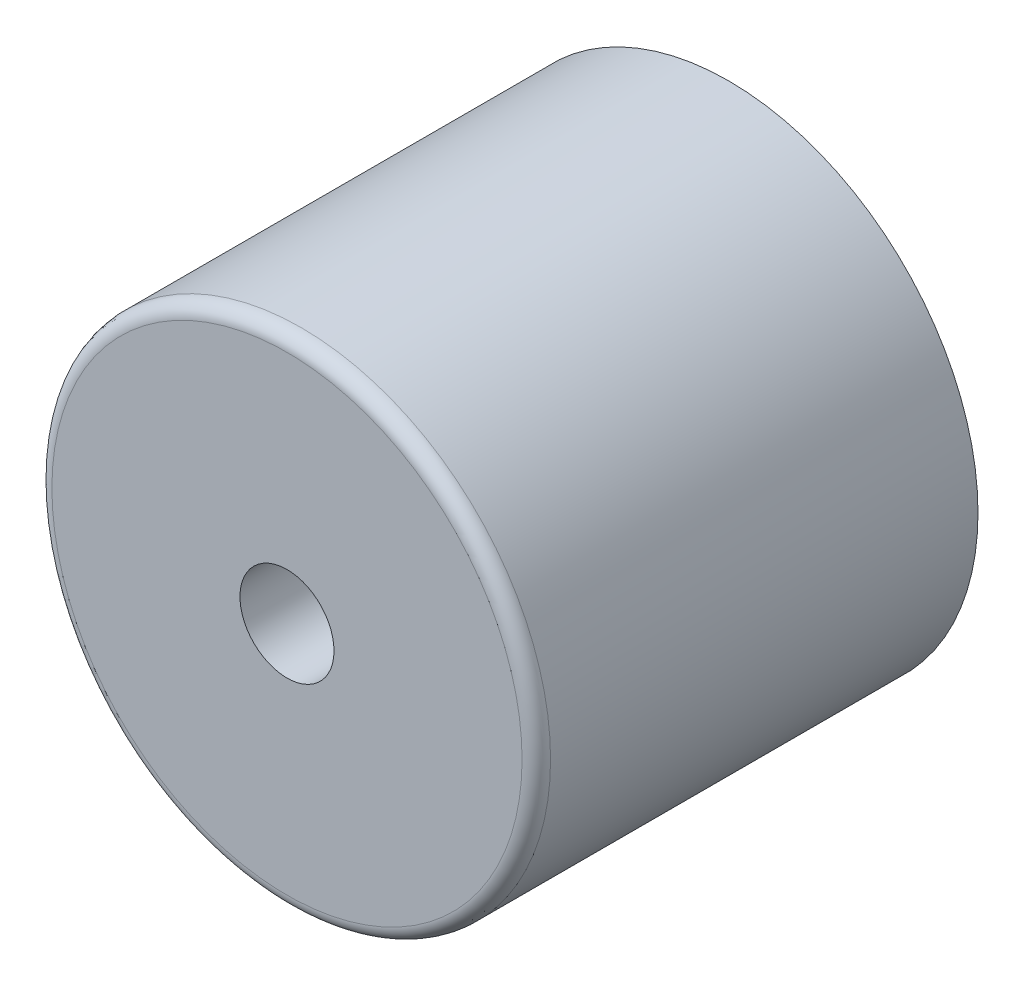
SolidWorks part; units mm, degrees
ref_plane "Piano frontale" through (0, 0, 0) normal (0, 0, 1) x (1, 0, 0)
ref_plane "Piano superiore" through (0, 0, 0) normal (0, 1, 0) x (1, 0, 0)
ref_plane "Piano destro" through (0, 0, 0) normal (1, 0, 0) x (0, 0, -1)
sketch "Schizzo1" plane through (0, 0, 0) normal (0, 0, 1) x (1, 0, 0)
  circle A0 centre (0, 0) radius 17.5
  dimension "D1" = 35
extrude "Estrusione-Estrusione1" add sketch "Schizzo1" along normal blind 31
fillet "Raccordo1" radius 1 1 edges at (17.5, 0, 31)
sketch "Schizzo2" plane through (0, 0, 0) normal (0, 0, -1) x (-1, 0, 0)
  circle A0 centre (0, 0) radius 14.25
  dimension "D1" = 28.5
extrude "Taglio-Estrusione1" cut sketch "Schizzo2" against normal blind 14
sketch "Schizzo3" plane through (0, 0, 0) normal (0, 1, 0) x (1, 0, 0)
  line L1 (16, 0) -> (14.25, 0)
  line L2 (17.5, 0) -> (16, 0) construction
  line L3 (14.25, 0) -> (-14.25, 0) construction
  line L4 (14.25, 0) -> (-14.25, 0) construction
  line L5 (14.25, 0) -> (14.25, -6)
  line L6 (16, 0) -> (14.25, -6)
  line L7 (0, 0) -> (0, -14.3058) construction
  dimension "D1" = 1.5
  dimension "D2" = 17.5
  dimension "D3" = 6
revolve "Taglia-Rivoluzione1" cut sketch "Schizzo3" angle 360 about L7
sketch "Schizzo4" plane through (0, 0, 0) normal (0, 1, 0) x (1, 0, 0)
  line L0 (14.25, -14) -> (-14.25, -14) construction
  line L1 (14.25, -14) -> (-14.25, -14) construction
  line L2 (0.25, -14) -> (0.25, -18.7)
  line L3 (0.25, -18.7) -> (9.25, -14)
  line L4 (9.25, -14) -> (0.25, -14)
  line L5 (0, -14) -> (0, -20.9981) construction
  point P4 (0, -14)
  point P6 (4.75, -14)
  dimension "D1" = 9
  dimension "D2" = 4.7
  dimension "D3" = 0.25
revolve "Taglia-Rivoluzione2" cut sketch "Schizzo4" angle 360 about L5 region at (3.25, 0, 15.5667)
sketch "Schizzo5" plane through (0, 0, 14) normal (0, 0, -1) x (-1, 0, 0)
  circle A0 centre (0, 0) radius 0.25
extrude "Taglio-Estrusione2" cut sketch "Schizzo5" against normal blind 4.7
hole_wizard "Foro per Vite M6-1" positions "Schizzo3D1" profile "Schizzo6" hole size "M6" standard "ISO" end condition through all
sketch3d "Schizzo3D1"
  line L0 (0, 0, 20.0985) -> (0, 0, 49.803) construction
  point P0 (0, 0, 31)
sketch "Schizzo6" plane through (0, 0, 31) normal (1, 0, 0) x (0, -1, 0)
  line L0 (0, 0) -> (0, 31)
  line L1 (0, 31) -> (3.3, 31)
  line L2 (3.3, 31) -> (3.3, 0)
  line L5 (3.3, 0) -> (0, 0)
  line L11 (0, -6.35) -> (0, 107.95) construction
  dimension "Thru Hole Dia." = 6.6
  dimension "Thru Hole Depth" = 31
